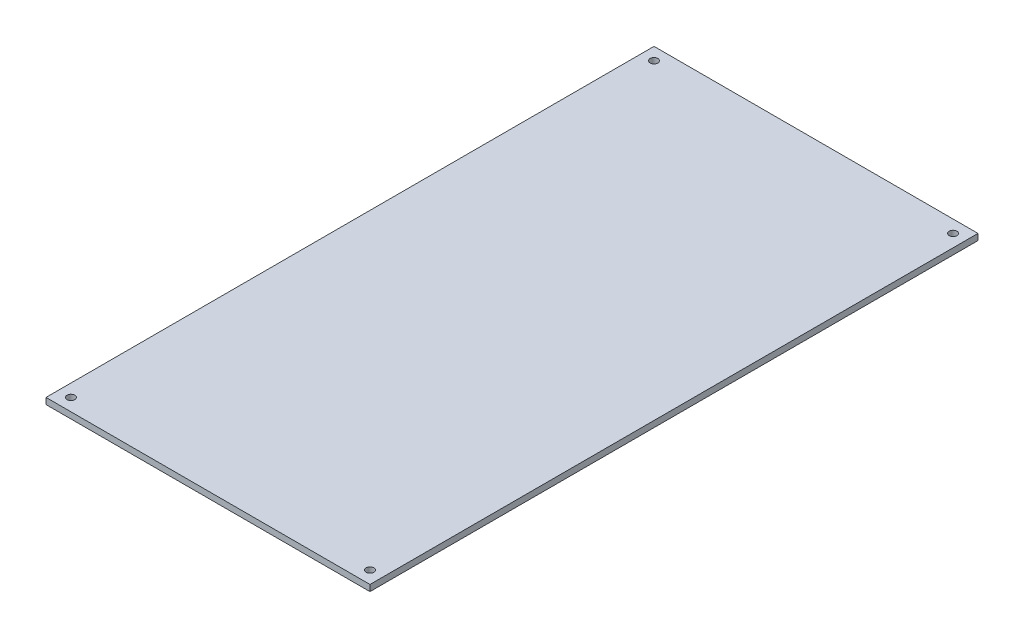
SolidWorks part; units mm, degrees
ref_plane "Front Plane" through (0, 0, 0) normal (0, 0, 1) x (1, 0, 0)
ref_plane "Top Plane" through (0, 0, 0) normal (0, 1, 0) x (1, 0, 0)
ref_plane "Right Plane" through (0, 0, 0) normal (1, 0, 0) x (0, 0, -1)
sketch "Sketch1" plane through (0, -91.8972, 0) normal (0, 1, 0) x (1, 0, 0)
  line L1 (-799.2, 626.1453) -> (-469, 626.1453)
  line L2 (-799.2, 626.1453) -> (-799.2, 6.4453)
  line L3 (-799.2, 6.4453) -> (-469, 6.4453)
  line L4 (-469, 626.1453) -> (-469, 6.4453)
  circle A0 centre (-786.5, 19.1453) radius 3.1293 construction
  circle A1 centre (-481.7, 19.1453) radius 3.9687 construction
  circle A2 centre (-481.7, 19.1453) radius 3.1293 construction
  circle A3 centre (-786.5, 613.4453) radius 3.1293 construction
  circle A4 centre (-481.7, 613.4453) radius 3.9687 construction
  circle A5 centre (-481.7, 613.4453) radius 3.9687
  circle A6 centre (-786.5, 613.4453) radius 3.9687 construction
  circle A7 centre (-786.5, 613.4453) radius 3.9687
  circle A8 centre (-786.5, 19.1453) radius 3.9687 construction
  circle A9 centre (-786.5, 19.1453) radius 3.9687
  circle A10 centre (-481.7, 19.1453) radius 3.9687
  line M1 (-780.3176, 23.0874) -> (-786.8228, 26.4705)
  line M2 (-786.8228, 26.4705) -> (-793.0053, 22.5283)
  line M5 (-786.1772, 11.82) -> (-779.9947, 15.7622)
  line M6 (-779.9947, 15.7622) -> (-780.3176, 23.0874)
  circle M7 centre (-786.5, 19.1453) radius 3.9688
extrude "Boss-Extrude1" add sketch "Sketch1" along normal blind 6.35 contours A10 L4 A5 L1 A7 L2 L3 M2 M1 M6 M5 | A10 L3 L4 | L3 L2 M7 M5 M6 M1 M2 | L2 L3 M7 | A5 L4 L1 | A7 L1 L2 region at (-634.1, -91.8972, -316.2953)
